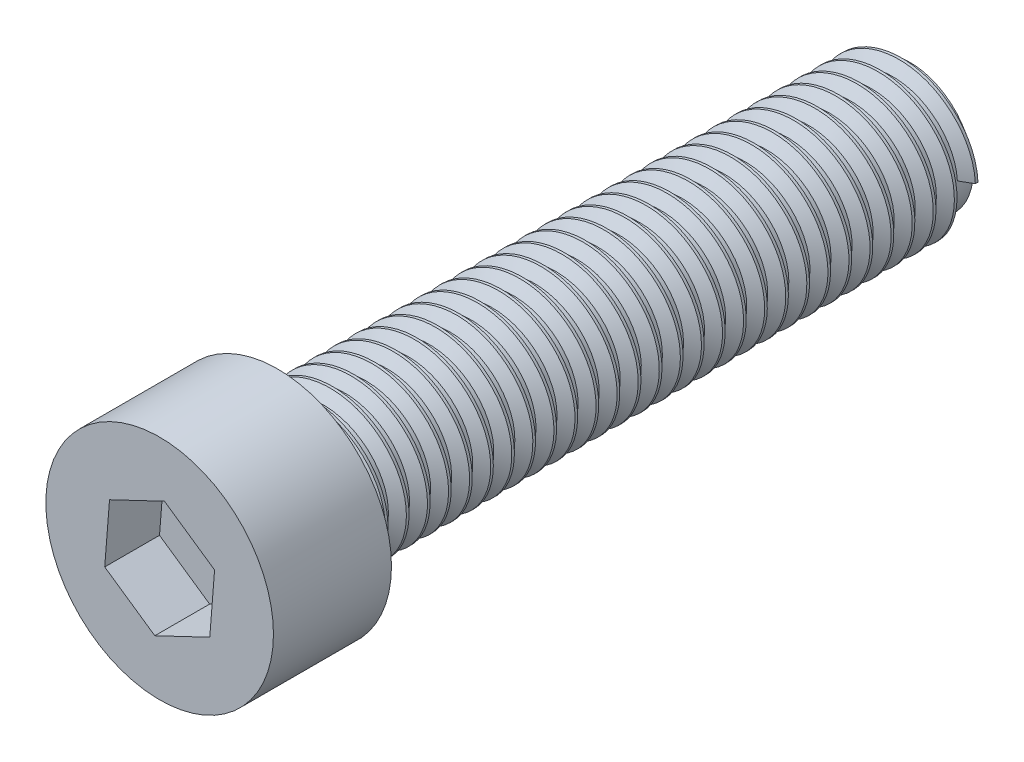
SolidWorks part; units mm, degrees
ref_plane "Front Plane" through (0, 0, 0) normal (0, 0, 1) x (1, 0, 0)
ref_plane "Top Plane" through (0, 0, 0) normal (0, 1, 0) x (1, 0, 0)
ref_plane "Right Plane" through (0, 0, 0) normal (1, 0, 0) x (0, 0, -1)
sketch "Sketch1" plane through (0, 0, 0) normal (0, 0, 1) x (1, 0, 0)
  circle A0 centre (0, 0) radius 2.7
  dimension "D1" = 5.4
extrude "Boss-Extrude1" add sketch "Sketch1" along normal blind 2.8
sketch "Sketch2" plane through (0, 0, 2.8) normal (0, 0, 1) x (1, 0, 0)
  line L1 (1.1889, -0.8184) -> (1.3032, 0.6204)
  line L2 (1.3032, 0.6204) -> (0.1143, 1.4388)
  line L3 (0.1143, 1.4388) -> (-1.1889, 0.8184)
  line L4 (-1.1889, 0.8184) -> (-1.3032, -0.6204)
  line L5 (-1.3032, -0.6204) -> (-0.1143, -1.4388)
  line L6 (-0.1143, -1.4388) -> (1.1889, -0.8184)
  circle A0 centre (0, 0) radius 1.25 construction
  dimension "D1" = 2.5
extrude "Cut-Extrude1" cut sketch "Sketch2" against normal blind 1.3
sketch "Sketch3" plane through (0, 0, 0) normal (0, 0, -1) x (-1, 0, 0)
  circle A0 centre (0, 0) radius 1.5
  dimension "D1" = 3
extrude "Boss-Extrude2" add sketch "Sketch3" along normal blind 15
thread "Thread1" pitch 0.5 start angle 0, offset 0, length 0, pitch 0.5, diameter 3
ref_plane "Plane1" through (1.5, 0, -15) normal (0, -1, 0) x (1, 0, 0)
sketch "Thread Profile1" plane through (1.5, 0, -15) normal (0, -1, 0) x (1, 0, 0)
  line L0 (0, 0) -> (0, 0.5) construction
  line L1 (0, 0) -> (0.2706, 0.1562)
  line L2 (0.2706, 0.1562) -> (0.2706, 0.2187)
  line L3 (0.2706, 0.2187) -> (0, 0.375)
  line L4 (0.2706, 0.1875) -> (0, 0.1875) construction
  line L11 (0, 0) -> (0, 0.375)
  point P2 (0, 0)
  dimension "Pitch" = 0.5
  dimension "Profile_Angle" = 60
  dimension "Profile_Land" = 0.0625
  dimension "Profile_Height" = 0.2706
